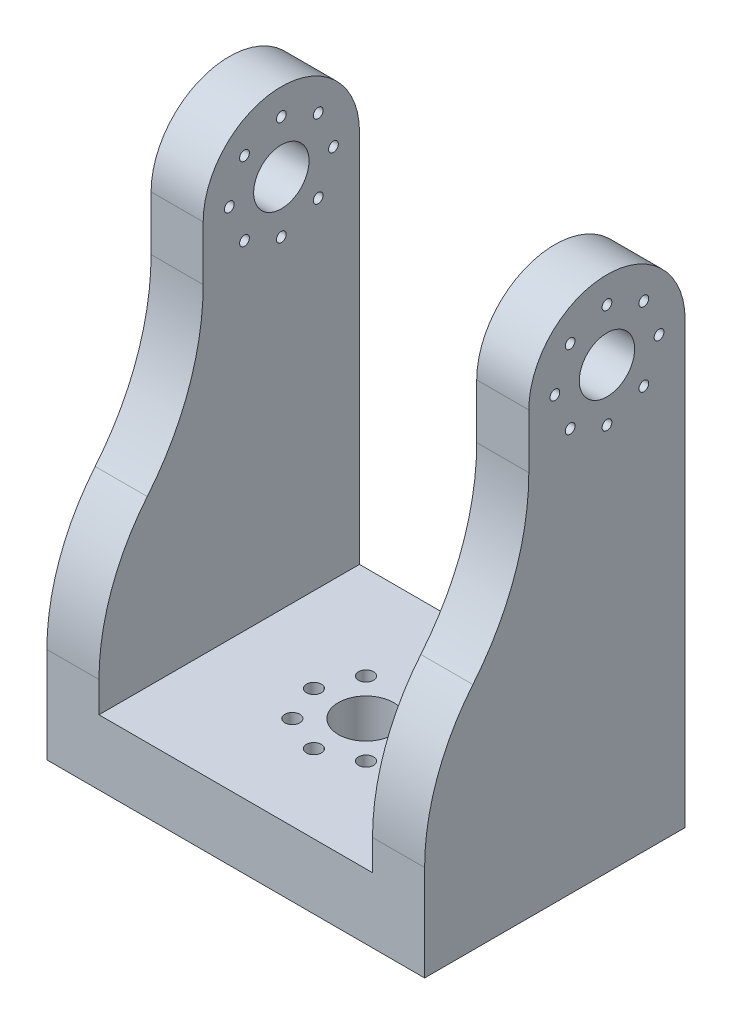
SolidWorks part; units mm, degrees
note: The reader was unsure of these and kept them because the rebuilt part matched: shared geometry of "Szkic3<3>".
material "ABS"
ref_plane "Płaszczyzna przednia" through (0, 0, 0) normal (0, 0, 1) x (1, 0, 0)
ref_plane "Płaszczyzna górna" through (0, 0, 0) normal (0, 1, 0) x (1, 0, 0)
ref_plane "Płaszczyzna prawa" through (0, 0, 0) normal (1, 0, 0) x (0, 0, -1)
sketch "Szkic1" plane through (0, 0, 0) normal (0, 0, 1) x (1, 0, 0)
  line L0 (0, 0) -> (0, 80) construction
  line L1 (21, 10) -> (-21, 10)
  line L2 (-21, 10) -> (-21, 80)
  line L3 (-21, 80) -> (-29, 80)
  line L4 (-29, 80) -> (-29, 0)
  line L5 (-29, 0) -> (29, 0)
  line L6 (29, 80) -> (21, 80)
  line L7 (29, 80) -> (29, 0)
  line L8 (21, 10) -> (21, 80)
  point P12 (0, 10)
  dimension "D1" = 8
  dimension "D2" = 10
  dimension "D3" = 21
extrude "Dodanie-wyciągnięcie1" add sketch "Szkic1" along normal blind 40
sketch "Szkic2" plane through (29, 0, 0) normal (1, 0, 0) x (0, 0, -1)
  line L0 (0, 10.0851) -> (-40, 10.0851)
  line L1 (0, 0) -> (0, 80) construction
  line L2 (-40, 0) -> (-40, 80) construction
  line L4 (0, 67.5368) -> (0, 10.0851)
  line L5 (-40, 0) -> (-40, 80) construction
  line L6 (-24, 67.5368) -> (-24, 10.0851)
  line L7 (-40, 0) -> (-40, 14.6889)
  circle A0 centre (-12, 67.5368) radius 4.25
  arc A1 (0, 67.5368) -> (-23.5823, 70.6752) centre (-12, 67.5368) ccw
  circle A2 centre (-12, 67.5368) radius 12
  arc A4 (-32.585, 35.3152) -> (-24, 59.1961) centre (-61.5073, 59.1961) ccw
  arc A5 (-32.585, 35.3152) -> (-40, 14.6889) centre (-7.6043, 14.6889) ccw
  dimension "D1" = 24
  dimension "D2" = 8.5
extrude "Wytnij-wyciągnięcie1" cut sketch "Szkic2" against normal through all
sketch "Szkic3" plane through (0, 10, 0) normal (0, 1, 0) x (1, 0, 0)
  line L0 (0, 0) -> (0, -40) construction
  line L1 (21, -40) -> (-21, -40) construction
  circle A0 centre (0, -20) radius 4.25
  circle A1 centre (5.6569, -25.6569) radius 0.65
  circle A2 centre (8, -20) radius 0.65
  circle A3 centre (0, -28) radius 0.65
  circle A4 centre (-5.6569, -25.6569) radius 0.65
  circle A5 centre (-8, -20) radius 0.65
  circle A6 centre (-5.6569, -14.3431) radius 0.65
  circle A7 centre (0, -12) radius 0.65
  circle A8 centre (5.6569, -14.3431) radius 0.65
  circle A9 centre (8, -20) radius 1.15
  circle A10 centre (8, -20) radius 0.15
  circle A11 centre (5.6569, -25.6569) radius 1.15
  circle A12 centre (0, -28) radius 1.15
  circle A13 centre (-5.6569, -25.6569) radius 1.15
  circle A14 centre (-8, -20) radius 1.15
  circle A15 centre (-5.6569, -14.3431) radius 1.15
  circle A16 centre (0, -12) radius 1.15
  circle A17 centre (5.6569, -14.3431) radius 1.15
  point P18 (0, -20)
  point P26 (0, -20)
  point P45 (0, -20)
  dimension "D1" = 8
  dimension "D2" = 8.5
  dimension "D3" = 0.5
  dimension "D4" = 0.5
  dimension "D5" = 8
extrude "Wytnij-wyciągnięcie2" cut sketch "Szkic3" against normal through all contours L0 A7 | A7 L0 | A6 | A5 | A4 | L0 A3 | A3 L0 | A1 | L0 A0 | A0 L0 | A2 | A8
sketch "Szkic4" plane through (-29, 0, 0) normal (-1, 0, 0) x (0, 0, 1)
  line L0 (12, 67.5368) -> (-10.5554, 67.5368) construction
  circle A0 centre (4, 67.5368) radius 0.75
  circle A1 centre (12, 75.5368) radius 0.75
  circle A2 centre (20, 67.5368) radius 0.75
  circle A3 centre (12, 59.5368) radius 0.75
  circle A4 centre (6.3431, 61.8799) radius 0.75
  circle A5 centre (4, 67.5368) radius 0.75
  circle A6 centre (6.3431, 73.1936) radius 0.75
  circle A7 centre (12, 75.5368) radius 0.75
  circle A8 centre (17.6569, 73.1936) radius 0.75
  circle A9 centre (20, 67.5368) radius 0.75
  circle A10 centre (17.6569, 61.8799) radius 0.75
  point P2 (12, 67.5368)
  point P15 (12, 67.5368)
  point P29 (12, 67.5368)
  dimension "D1" = 8
  dimension "D3" = 1.5
  dimension "D4" = 8
  dimension "D2" = 4
extrude "Wytnij-wyciągnięcie3" cut sketch "Szkic4" against normal through all contours A1 | A8 | L0 A0 | A5 L0 | A4 | A10 | A2 | A3 | A6
extrude "Wytnij-wyciągnięcie4" cut sketch "Szkic3<3>" against normal blind 4 contours A9 A2 | A17 A8 | L0 A16 A7 | A16 L0 A7 | A15 A6 | A14 A5 | A13 A4 | L0 A12 A3 | A12 L0 A3 | A11 A1
sketch "Szkic3<3>" plane through (0, 10, 0) normal (0, 1, 0) x (1, 0, 0) same geometry as "Szkic3"
